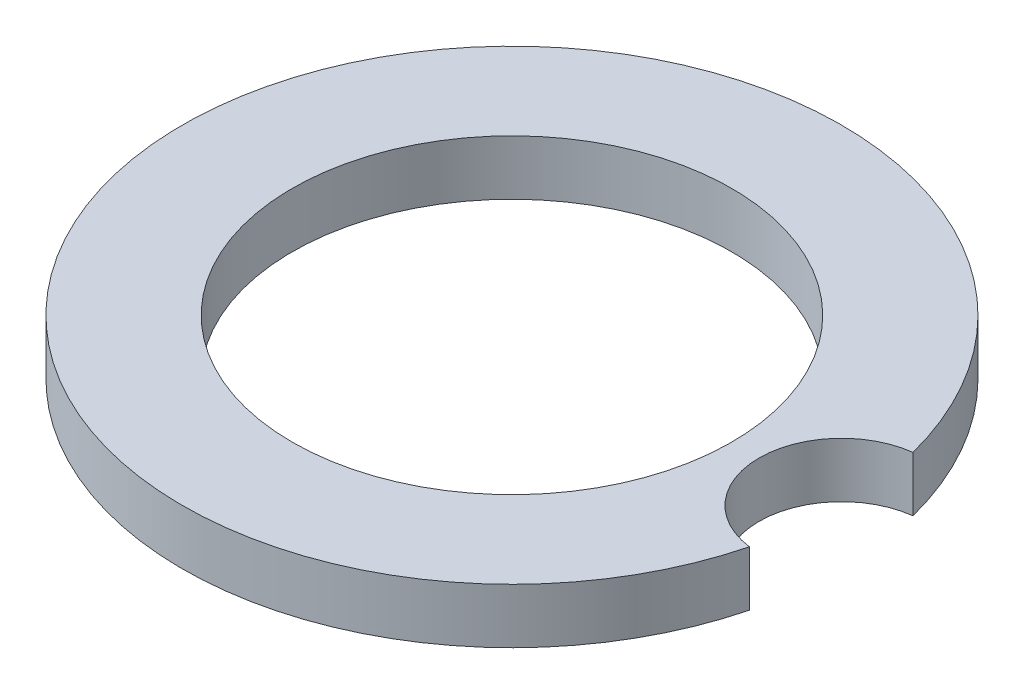
SolidWorks part; units mm, degrees
ref_plane "Front Plane" through (0, 0, 0) normal (0, 0, 1) x (1, 0, 0)
ref_plane "Top Plane" through (0, 0, 0) normal (0, 1, 0) x (1, 0, 0)
ref_plane "Right Plane" through (0, 0, 0) normal (1, 0, 0) x (0, 0, -1)
sketch "Sketch1" plane through (0, 0, 0) normal (0, 1, 0) x (1, 0, 0)
  circle A0 centre (0, 0) radius 50.8
  circle A1 centre (0, 0) radius 76.1746
  dimension "Front_CR_ID" = 101.6
  dimension "Front_CR_OD" = 152.3492
extrude "Boss-Extrude1" add sketch "Sketch1" along normal blind 12.7 contours A1
extrude "Cut-Extrude2" cut sketch "Sketch1<10>" along normal through all contours A0
sketch "Sketch1<10>" plane through (0, 0, 0) normal (0, 1, 0) x (1, 0, 0) same geometry as "Sketch1"
sketch "Sketch2" plane through (0, 12.7, 0) normal (0, 1, 0) x (1, 0, 0)
  line L0 (76.2, 19.05) -> (76.2, -19.05)
  arc A0 (76.2, 19.05) -> (76.2, -19.05) centre (76.1746, 0) ccw
  circle A1 centre (0, 0) radius 76.1746 construction
  dimension "D1" = 38.1
extrude "Cut-Extrude3" cut sketch "Sketch2" against normal through all contours A0 L0
ref_plane "Plane1" through (0, 6.35, 0) normal (0, -1, 0) x (-1, 0, 0)
equation "\"Bodytube_OD\"= 6.17in"
equation "\"Bodytube_ID\"= 5.998in"
equation "\"Motor_OD\"= 4in"
equation "\"Fwd_Tube_Length\"= 40in"
equation "\"Mid_Tube_Length\"= 1in"
equation "\"Aft_Section_Length\"= 39in"
equation "\"Mid_Coupler_Length\"= 13in"
equation "\"Aft_Lower_Length\"= 22in"
equation "\"AB_Coupler_OD_Length\"= 1in"
equation "\"AB_Coupling_Section_Length\"= 0.375in"
equation "\"AB_Coupler_Length\"= \"AB_Coupler_OD_Length\" + \"AB_Coupling_Section_Length\" * 2"
equation "\"Cutout_Angle\"= 80"
equation "\"AB_Paddle_Height\"= 0.375in"
equation "\"AB_Coupler_Num_Screws\"= 6"
equation "\"Num_Cutouts\"= 3"
equation "\"AB_Coupler_OD\"= 6.17in"
equation "\"AB_Coupler_ID\"= 5.75in"
equation "\"AB_Coupler_Surface_Diameter\"= 5.998in"
equation "\"AB_Coupling_Screw_Diameter\"= 0.1065in"
equation "\"AB_Central_Bushing_Length\"= .75in"
equation "\"Lead_Screw_Dist\"= 2.25in"
equation "\"Lead_Screw_Diam\"= 11mm"
equation "\"Lead_Screw_Length\"= (\"Mid_Coupler_Length\" + 2*0.375in + 2*0.5in)"
equation "\"Paddle_Pin_Offset\"= .25in"
equation "\"Paddle_Pin_Radius\"= 2.25in"
equation "\"Paddle_Gear_OD\"= 3.2in"
equation "\"Fwd_BKHD_From_Top\"= 18in"
equation "\"Front_CR_OD@Sketch1\"=\"Bodytube_ID\""
equation "\"Front_CR_ID@Sketch1\"=\"Motor_OD\""
